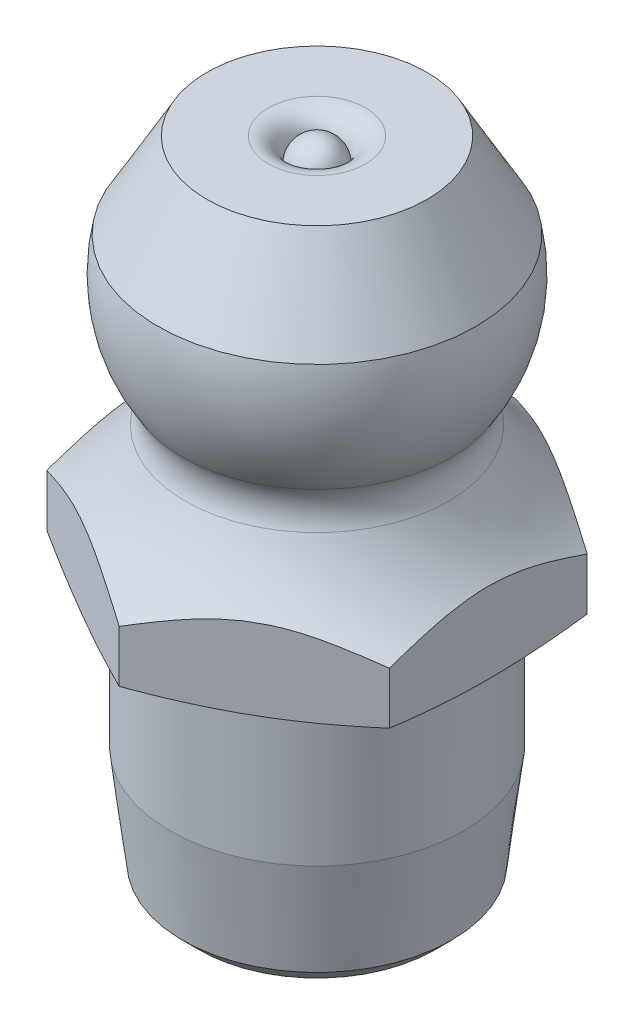
SolidWorks part; units mm, degrees
ref_plane "Plane1" through (0, 0, 0) normal (0, 0, 1) x (1, 0, 0)
ref_plane "Plane2" through (0, 0, 0) normal (0, 1, 0) x (1, 0, 0)
ref_plane "Plane3" through (0, 0, 0) normal (1, 0, 0) x (0, 0, -1)
sketch "support-top" plane through (0, 0, 0) normal (0, 1, 0) x (1, 0, 0)
  line L0 (0, -4.0415) -> (0, 4.0415) construction
  line L1 (0, 4.0415) -> (3.5, 2.0207)
  line L2 (3.5, 2.0207) -> (3.5, -2.0207)
  line L3 (3.5, -2.0207) -> (0, -4.0415)
  line L4 (-3.5, -2.0207) -> (0, -4.0415)
  line L5 (-3.5, 2.0207) -> (-3.5, -2.0207)
  line L6 (0, 4.0415) -> (-3.5, 2.0207)
  line L7 (4.0415, 0) -> (-4, 0) construction
  circle A0 centre (0, 0) radius 4.0415 construction
  circle A1 centre (0, 0) radius 3
  dimension "diam-thread" = 6
  dimension "width-key" = 7
sketch "support-front" plane through (0, 0, 0) normal (0, 0, 1) x (1, 0, 0)
  line L0 (0, 0) -> (0, 14.0771) construction
  line L1 (0.9928, 13.2) -> (2.25, 13.2)
  line L2 (0, 13.2) -> (-2.25, 13.2) construction
  line L3 (2.25, 13.2) -> (3.25, 11.4526)
  line L4 (-2.25, 13.2) -> (-3.25, 11.4526) construction
  line L5 (0, 10.7526) -> (3.3245, 10.7526) construction
  line L6 (0, 0) -> (2.7053, 0)
  line L7 (2.7053, 0) -> (3, 2.4)
  line L8 (-2.5, 8.5611) -> (2.5, 8.5611) construction
  line L9 (3, 5.2) -> (-3, 5.2) construction
  line L10 (3, 5.2) -> (4.0415, 5.4791)
  line L11 (0, 6.0103) -> (4.0415, 6.0103) construction
  line L12 (4.0415, 5.4791) -> (4.0415, 6.5415)
  line L13 (3, 2.4) -> (3.3438, 5.2) construction
  line L14 (-2.7053, 0) -> (0, 0) construction
  line L15 (-3, 2.4) -> (3, 2.4) construction
  line L16 (-4.0415, 5.4791) -> (-4.0415, 6.5415) construction
  line L17 (-3, 5.2) -> (-4.0415, 5.4791) construction
  line L18 (0, 12.7036) -> (2.5341, 12.7036) construction
  line L19 (0, 0) -> (0, 13.2)
  line L20 (3, 2.4) -> (3, 5.2)
  line L21 (-3, 2.4) -> (-3, 5.2) construction
  line L22 (3, 2.4) -> (3, 0) construction
  line L23 (-2.7053, 0) -> (-3, 2.4) construction
  line L24 (3, 5.2) -> (3.3438, 5.2) construction
  line L25 (2.4095, 0) -> (2.7467, 0.3373)
  line L26 (0, 0) -> (2.7467, 0.3373) construction
  arc A0 (3.25, 11.4526) -> (2.5, 8.5611) centre (0, 10.7526) ccw construction
  arc A1 (2.697, 8.086) -> (4.0415, 6.5415) centre (6.2858, 9.8526) ccw
  arc A2 (-2.697, 8.086) -> (-4.0415, 6.5415) centre (-6.2858, 9.8526) cw construction
  arc A3 (2.7524, 8.888) -> (3.25, 11.4526) centre (0, 10.7526) ccw
  arc A4 (2.7524, 8.888) -> (2.697, 8.086) centre (3.4148, 8.4393) ccw
  arc A5 (-2.7524, 8.888) -> (-2.697, 8.086) centre (-3.4148, 8.4393) cw construction
  arc A6 (0, 13.2) -> (0.4964, 12.7036) centre (0, 12.7036) cw
  arc A7 (0.4964, 12.7036) -> (0.9928, 13.2) centre (0.9928, 12.7036) cw
  dimension "D2" = 45
  dimension "rad-body" = 4
  dimension "rad-ball-start" = 0.8
  dimension "diam-top-ball" = 4.5
  dimension "diam-ball" = 6.5
  dimension "D3" = 7
  dimension "dist-angle-ball" = 0.7
  dimension "height" = 13.2
  dimension "dist-rad-body" = 0.9
  dimension "diam-ball-start" = 5
  dimension "angle-thread" = 7
  dimension "dist-thread" = 2.4
  dimension "D10" = 15
  dimension "length-thread" = 5.2
  dimension "D14" = 0.4964
sketch "support-thread" plane through (0, 0, 0) normal (0, 0, 1) x (1, 0, 0)
  line L0 (3.3881, 4.6901) -> (2.4607, 4.6901) construction
  line L1 (3.4589, 5.2664) -> (2.4607, 4.6901)
  line L2 (3.3267, 4.1901) -> (2.4607, 4.6901)
  line L3 (2.6772, 4.8151) -> (2.6772, 4.5651)
  line L4 (3.4589, 5.2664) -> (3.3267, 4.1901)
  line L5 (3.3267, 4.1901) -> (4.2541, 4.1901) construction
  line L6 (3.3267, 4.1901) -> (2.4607, 3.6901)
  line L8 (3.2269, 4.2478) -> (3.2116, 4.1237)
  line L9 (3, 2.4) -> (3.3438, 5.2) construction
  arc A0 (2.6231, 4.7839) -> (2.6231, 4.5964) centre (2.6772, 4.6901) ccw
  point P7 (2.6772, 4.6901)
  dimension "angle-thread" = 60
  dimension "pitch" = 1
  dimension "width-thread-bottom" = 0.25
  dimension "width-thread-top" = 0.125
ref_plane "support-plane-thread" through (0, 5.2, 0) normal (0, 1, 0) x (-1, 0, 0)
sketch "Sketch6" plane through (0, 0, 0) normal (0, 0, 1) x (1, 0, 0)
  line L0 (0, 0) -> (0, 13.2) construction
  line L1 (0.9928, 13.2) -> (2.25, 13.2) construction
  line L2 (2.25, 13.2) -> (3.25, 11.4526) construction
  line L3 (4.0415, 5.4791) -> (4.0415, 6.5415) construction
  line L4 (3, 5.2) -> (4.0415, 5.4791) construction
  line L6 (0, 0) -> (2.7053, 0) construction
  line L7 (0, 0) -> (0, 13.2) construction
  line L8 (0.9928, 13.2) -> (2.25, 13.2)
  line L9 (2.25, 13.2) -> (3.25, 11.4526)
  line L10 (4.0415, 5.4791) -> (4.0415, 6.5415)
  line L11 (3, 5.2) -> (4.0415, 5.4791)
  line L12 (3, 2.4) -> (3, 5.2) construction
  line L13 (0, 0) -> (2.4095, 0)
  line L14 (0, 0) -> (0, 13.2)
  line L15 (2.7053, 0) -> (3, 2.4) construction
  line L16 (3, 2.4) -> (3, 5.2)
  line L17 (2.7467, 0.3373) -> (3, 2.4)
  line L18 (2.4095, 0) -> (2.7467, 0.3373) construction
  line L19 (2.4095, 0) -> (2.7467, 0.3373)
  arc A0 (0.4964, 12.7036) -> (0, 13.2) centre (0, 12.7036) ccw construction
  arc A1 (0.9928, 13.2) -> (0.4964, 12.7036) centre (0.9928, 12.7036) ccw construction
  arc A2 (2.7524, 8.888) -> (3.25, 11.4526) centre (0, 10.7526) ccw construction
  arc A3 (2.7524, 8.888) -> (2.697, 8.086) centre (3.4148, 8.4393) ccw construction
  arc A4 (2.697, 8.086) -> (4.0415, 6.5415) centre (6.2858, 9.8526) ccw construction
  arc A5 (0.4964, 12.7036) -> (0, 13.2) centre (0, 12.7036) ccw
  arc A6 (0.9928, 13.2) -> (0.4964, 12.7036) centre (0.9928, 12.7036) ccw
  arc A7 (2.7524, 8.888) -> (3.25, 11.4526) centre (0, 10.7526) ccw
  arc A8 (2.7524, 8.888) -> (2.697, 8.086) centre (3.4148, 8.4393) ccw
  arc A9 (2.697, 8.086) -> (4.0415, 6.5415) centre (6.2858, 9.8526) ccw
revolve "body" add sketch "Sketch6" angle 360 about L7
sketch "Sketch4" plane through (0, 0, 0) normal (0, 1, 0) x (1, 0, 0)
  line L6 (3.5, -2.0207) -> (3.5, 2.0207)
  line L7 (3.5, 2.0207) -> (0, 4.0415)
  line L8 (0, 4.0415) -> (-3.5, 2.0207)
  line L9 (-3.5, 2.0207) -> (-3.5, -2.0207)
  line L10 (-3.5, -2.0207) -> (0, -4.0415)
  line L11 (0, -4.0415) -> (3.5, -2.0207)
  line L12 (3.5, -2.0207) -> (3.5, 2.0207)
  line L13 (3.5, 2.0207) -> (0, 4.0415)
  line L14 (0, 4.0415) -> (-3.5, 2.0207)
  line L15 (-3.5, 2.0207) -> (-3.5, -2.0207)
  line L16 (-3.5, -2.0207) -> (0, -4.0415)
  line L17 (0, -4.0415) -> (3.5, -2.0207)
  dimension "D1" = 0
extrude "cut-key" cut sketch "Sketch4" along normal through all flip side to cut
sketch "Sketch11" plane through (0, 0, 0) normal (0, 0, 1) x (1, 0, 0)
  line L0 (3, 5.2) -> (4.0415, 5.4791) construction
  line L1 (3, 2.4) -> (3, 5.2) construction
  line L2 (3, 5.2) -> (3.1917, 5.2514)
  line L3 (3, 5.0015) -> (3, 5.2)
  line L4 (3.4589, 5.2664) -> (2.4607, 4.6901) construction
  line L5 (0, 0) -> (0, 13.2) construction
  line L6 (0, 0) -> (0, 13.2) construction
  arc A0 (3, 5.0015) -> (3.1917, 5.2514) centre (3.2587, 5.0015) cw
revolve "body-fillet" [suppressed] add sketch "Sketch11" angle 360 about L6
sketch "Sketch8" plane through (0, 0, 0) normal (0, 0, 1) x (1, 0, 0)
  line L0 (0, 0) -> (0, 13.2) construction
  line L3 (3.3267, 4.1901) -> (2.4607, 4.6901) construction
  line L4 (3.4589, 5.2664) -> (2.4607, 4.6901) construction
  line L5 (0, 0) -> (0, 13.2) construction
  line L6 (3.2269, 4.2478) -> (3.2116, 4.1237) construction
  line L7 (3.2269, 4.2478) -> (3.3438, 5.2)
  line L8 (3.2269, 4.2478) -> (2.6231, 4.5964)
  line L9 (3.3438, 5.2) -> (2.6231, 4.7839)
  arc A0 (2.6231, 4.7839) -> (2.6231, 4.5964) centre (2.6772, 4.6901) ccw construction
  arc A1 (2.6231, 4.7839) -> (2.6231, 4.5964) centre (2.6772, 4.6901) ccw
revolve "thread-notch" [suppressed] cut sketch "Sketch8" angle 360 about L5
sketch "Sketch9" plane through (0, 5.2, 0) normal (0, 1, 0) x (-1, 0, 0)
  circle A0 centre (0, 0) radius 3 construction
  circle A1 centre (0, 0) radius 3
curve "helix" parameters "height-thread"=5.7, "pitch"=1
sketch "Sketch10" plane through (0, 0, 0) normal (0, 0, 1) x (1, 0, 0)
  line L2 (3.4589, 5.2664) -> (2.4607, 4.6901) construction
  line L3 (3.3267, 4.1901) -> (2.4607, 4.6901) construction
  line L6 (3.3438, 5.2) -> (2.6231, 4.7839)
  line L7 (3.2269, 4.2478) -> (2.6231, 4.5964)
  line L11 (3, 2.4) -> (3.3438, 5.2) construction
  line L12 (3.2269, 4.2478) -> (3.3438, 5.2)
  arc A0 (2.6231, 4.7839) -> (2.6231, 4.5964) centre (2.6772, 4.6901) ccw construction
  arc A1 (2.6231, 4.7839) -> (2.6231, 4.5964) centre (2.6772, 4.6901) ccw
sweep "thread-helix" [suppressed] cut profiles "Sketch10" path "helix"
ref_plane "ref-plane-top" through (0, 5.2, 0) normal (0, 1, 0) x (-1, 0, 0)
ref_axis "ref-axis-center" through (0, -50, 0) along (0, 1, 0)
ref_axis "ref-axis-lubrication" through (0, -50, 0) along (0, 1, 0)
equation "\"width-thread-bottom@support-thread\" = \"pitch@support-thread\" / 4"
equation "\"width-thread-top@support-thread\" = \"pitch@support-thread\" / 8"
equation "\"pitch@helix\" = \"pitch@support-thread\""
equation "\"height-thread@helix\" = \"length-thread@support-front\" + 0.5"
